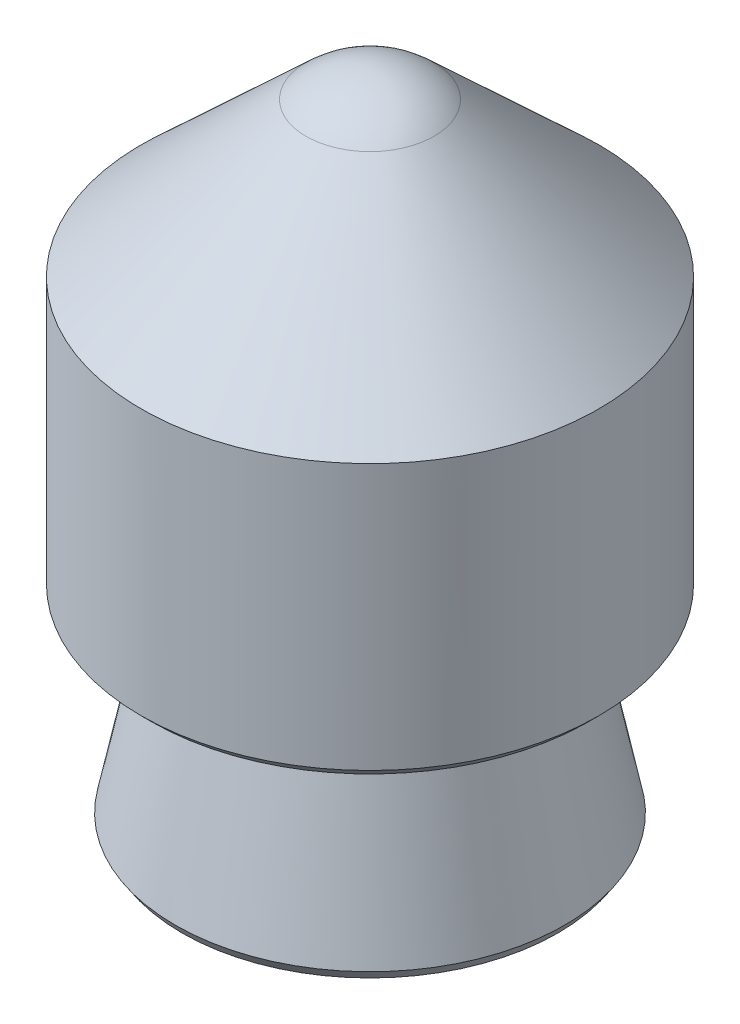
SolidWorks part; units mm, degrees
material "6061-T6 (SS)"
ref_plane "Front Plane" through (0, 0, 0) normal (0, 0, 1) x (1, 0, 0)
ref_plane "Top Plane" through (0, 0, 0) normal (0, 1, 0) x (1, 0, 0)
ref_plane "Right Plane" through (0, 0, 0) normal (1, 0, 0) x (0, 0, -1)
sketch "Sketch1" plane through (0, 0, 0) normal (0, 0, 1) x (1, 0, 0)
  line L0 (0, 25.4) -> (0, 41.3512) construction
  line L2 (4.7085, 14.7066) -> (-4.7085, 14.7066) construction
  line L3 (0, 25.4) -> (-4.8069, 25.4)
  line L4 (-3.8227, 30.2387) -> (-4.8069, 25.4)
  line L5 (0, 25.4) -> (0, 41.3512)
  line L6 (-3.8227, 30.2387) -> (-5.588, 30.2387)
  line L7 (-5.588, 30.2387) -> (-5.588, 36.9824)
  line L8 (-1.5634, 40.7354) -> (-5.588, 36.9824)
  arc A0 (-1.5634, 40.7354) -> (0, 41.3512) centre (0, 39.0588) cw
  dimension "D6" = 2.2923
  dimension "D1" = 26.6446
  dimension "D2" = 3.8227
  dimension "D3" = 11.176
  dimension "D4" = 6.7437
  dimension "D5" = 11.1125
  dimension "D7" = 4.8069
revolve "Revolve1" add sketch "Sketch1" angle 360 about L0
chamfer "Chamfer1" distance 0.254 angle 45 2 edges at (0, 25.4, -4.8069) (0, 30.2387, -5.588) first distance on face at (0, 25.4, -4.8069) first distance on face at (0, 30.2387, -5.588)
sketch "Sketch4" plane through (0, 25.4, 0) normal (0, -1, 0) x (1, 0, 0)
  circle A0 centre (0, 0) radius 3.5
  dimension "D1" = 7
extrude "Cut-Extrude1" cut sketch "Sketch4" against normal blind 2.5
hole_wizard "M7x0.75 Tapped Hole1" positions "Sketch5" profile "Sketch6" tap size "M7X0.75" standard "ANSI Metric"
sketch "Sketch5" plane through (0, 25.4, 0) normal (0, -1, 0) x (-1, 0, 0)
  point P0 (0, 0)
  point P3 (96.1394, -180.6847)
sketch "Sketch6" plane through (0, 25.4, 0) normal (1, 0, 0) x (0, 0, -1)
  line L0 (0, 0) -> (0, 12.7246)
  line L1 (0, 12.7246) -> (3, 10.922)
  line L2 (3, 10.922) -> (3, 0)
  line L5 (3, 0) -> (0, 0)
  line L10 (0, 12.7246) -> (-3, 10.922) construction
  line L11 (0, -6.35) -> (0, 107.95) construction
  dimension "Tap Drill Dia." = 6
  dimension "Tap Drill Depth" = 10.922
  dimension "Drill Angle" = 118
cosmetic thread "Hole Thread1" parameters "D1"=9.906, "D2"=7
